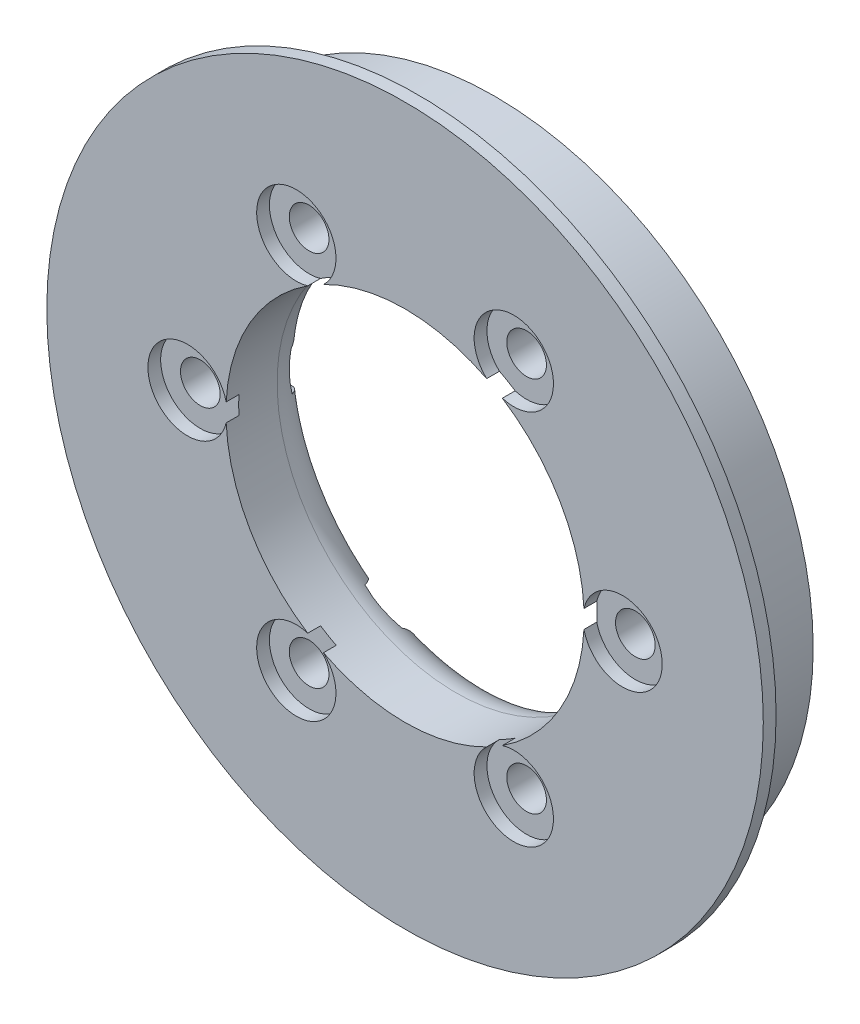
SolidWorks part; units mm, degrees
material "聚脂树脂"
ref_plane "前视基准面" through (0, 0, 0) normal (0, 0, 1) x (1, 0, 0)
ref_plane "上视基准面" through (0, 0, 0) normal (0, 1, 0) x (1, 0, 0)
ref_plane "右视基准面" through (0, 0, 0) normal (1, 0, 0) x (0, 0, -1)
sketch "草图1" plane through (0, 0, 0) normal (0, 0, 1) x (1, 0, 0)
  line L0 (0, 0) -> (17, 0)
  circle A0 centre (0, 0) radius 24.9
  circle A1 centre (0, 0) radius 14
  dimension "D1" = 49.8
  dimension "D2" = 28
  dimension "D3" = 17
extrude "凸台-拉伸1" add sketch "草图1" along normal blind 7 contours A0 A1 region at (-24.1957, 0, 0)
sketch "草图3" plane through (0, 0, 0) normal (0, 0, -1) x (-1, 0, 0)
  circle A0 centre (8.5, -14.7224) radius 1.55 construction
  circle A1 centre (-8.5, -14.7224) radius 1.55 construction
  circle A2 centre (-17, 0) radius 1.55 construction
  circle A3 centre (-8.5, 14.7224) radius 1.55 construction
  circle A4 centre (17, 0) radius 1.55 construction
  circle A5 centre (8.5, 14.7224) radius 1.55 construction
  circle A6 centre (8.5, -14.7224) radius 1.55
  circle A7 centre (-8.5, -14.7224) radius 1.55
  circle A8 centre (-17, 0) radius 1.55
  circle A9 centre (-8.5, 14.7224) radius 1.55
  circle A10 centre (17, 0) radius 1.55
  circle A11 centre (8.5, 14.7224) radius 1.55
extrude "切除-拉伸2" cut sketch "草图3" against normal blind 10
sketch "草图4" plane through (0, 0, 7) normal (0, 0, 1) x (1, 0, 0)
  circle A0 centre (17, 0) radius 3.1
  circle A2 centre (8.5, -14.7224) radius 3.1
  circle A3 centre (-8.5, -14.7224) radius 3.1
  circle A4 centre (-17, 0) radius 3.1
  circle A5 centre (-8.5, 14.7224) radius 3.1
  circle A6 centre (8.5, 14.7224) radius 3.1
  point P15 (0, 0)
  dimension "D1" = 6.2
  dimension "D2" = 6
extrude "切除-拉伸3" cut sketch "草图4" against normal blind 1
sketch "草图5" plane through (0, 0, 7) normal (0, 0, 1) x (1, 0, 0)
  circle A0 centre (0, 0) radius 28
sketch "草图6" plane through (0, 0, 7) normal (0, 0, 1) x (1, 0, 0)
  circle A0 centre (0, 0) radius 24.9 construction
  circle A1 centre (0, 0) radius 24.9
  circle A2 centre (0, 0) radius 28 construction
  circle A3 centre (0, 0) radius 28
extrude "凸台-拉伸2" add sketch "草图6" against normal blind 1
sketch "草图7" plane through (0, 0, 0) normal (0, 0, -1) x (-1, 0, 0)
  line L0 (8.5754, -17.897) -> (11.2869, -16.2444)
  line L1 (19.7869, -1.522) -> (19.7115, 1.6526)
  line L2 (19.7115, 1.6526) -> (16.9246, 3.1745)
  line L3 (16.9246, 3.1745) -> (14.2131, 1.522)
  line L4 (14.2131, 1.522) -> (14.2885, -1.6526)
  line L5 (14.2885, -1.6526) -> (17.0754, -3.1745)
  line L6 (17.0754, -3.1745) -> (19.7869, -1.522)
  line L7 (11.2869, -16.2444) -> (11.2115, -13.0699)
  line L8 (11.2115, -13.0699) -> (8.4246, -11.5479)
  line L9 (8.4246, -11.5479) -> (5.7131, -13.2005)
  line L10 (5.7131, -13.2005) -> (5.7885, -16.375)
  line L11 (5.7885, -16.375) -> (8.5754, -17.897)
  line L12 (-11.2115, -16.375) -> (-8.4246, -17.897)
  line L13 (-8.4246, -17.897) -> (-5.7131, -16.2444)
  line L14 (-5.7131, -16.2444) -> (-5.7885, -13.0699)
  line L15 (-5.7885, -13.0699) -> (-8.5754, -11.5479)
  line L16 (-8.5754, -11.5479) -> (-11.2869, -13.2005)
  line L17 (-11.2869, -13.2005) -> (-11.2115, -16.375)
  line L18 (-19.7869, 1.522) -> (-19.7115, -1.6526)
  line L19 (-19.7115, -1.6526) -> (-16.9246, -3.1745)
  line L20 (-16.9246, -3.1745) -> (-14.2131, -1.522)
  line L21 (-14.2131, -1.522) -> (-14.2885, 1.6526)
  line L22 (-14.2885, 1.6526) -> (-17.0754, 3.1745)
  line L23 (-17.0754, 3.1745) -> (-19.7869, 1.522)
  line L24 (-8.5754, 17.897) -> (-11.2869, 16.2444)
  line L25 (-11.2869, 16.2444) -> (-11.2115, 13.0699)
  line L26 (-11.2115, 13.0699) -> (-8.4246, 11.5479)
  line L27 (-8.4246, 11.5479) -> (-5.7131, 13.2005)
  line L28 (-5.7131, 13.2005) -> (-5.7885, 16.375)
  line L29 (-5.7885, 16.375) -> (-8.5754, 17.897)
  line L30 (11.2115, 16.375) -> (8.4246, 17.897)
  line L31 (8.4246, 17.897) -> (5.7131, 16.2444)
  line L32 (5.7131, 16.2444) -> (5.7885, 13.0699)
  line L33 (5.7885, 13.0699) -> (8.5754, 11.5479)
  line L34 (8.5754, 11.5479) -> (11.2869, 13.2005)
  line L35 (11.2869, 13.2005) -> (11.2115, 16.375)
  circle A0 centre (17, 0) radius 2.75 construction
  point P41 (0, 0)
  dimension "D1" = 6
extrude "切除-拉伸4" cut sketch "草图7" against normal blind 2.8
fillet "圆角1" radius 3 1 edges at (14, 0, 0)
